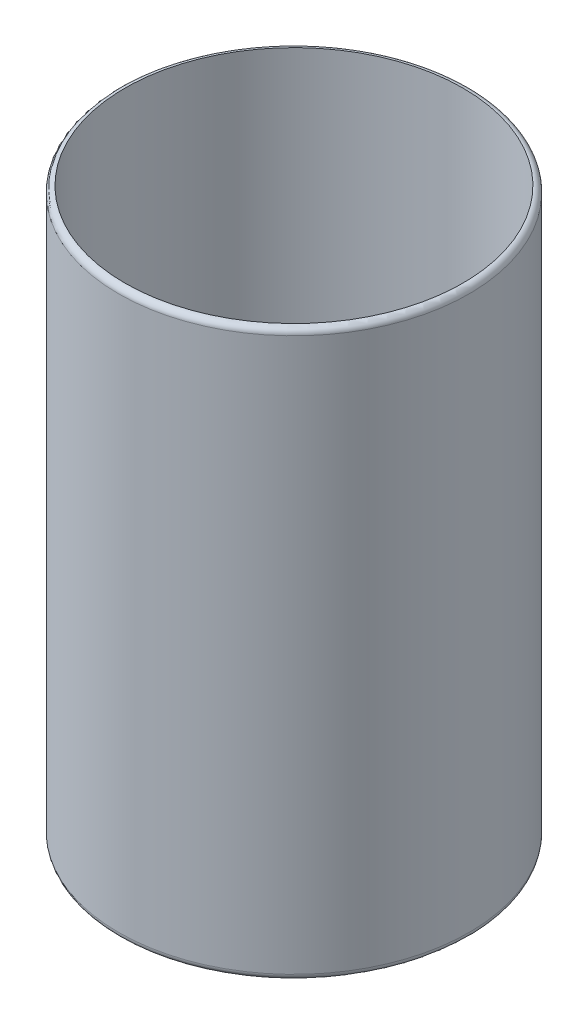
SolidWorks part; units mm, degrees
ref_plane "Front Plane" through (0, 0, 0) normal (0, 0, 1) x (1, 0, 0)
ref_plane "Top Plane" through (0, 0, 0) normal (0, 1, 0) x (1, 0, 0)
ref_plane "Right Plane" through (0, 0, 0) normal (1, 0, 0) x (0, 0, -1)
sketch "Sketch1" plane through (0, 0, 0) normal (0, 1, 0) x (1, 0, 0)
  circle A0 centre (0, 0) radius 14.1
  dimension "D1" = 28.2
extrude "Boss-Extrude1" add sketch "Sketch1" along normal blind 0.5
sketch "Sketch2" plane through (0, 0.5, 0) normal (0, 1, 0) x (1, 0, 0)
  circle A0 centre (0, 0) radius 13.6
  circle A1 centre (0, 0) radius 14.1
  circle A2 centre (0, 0) radius 14.1
  dimension "D1" = 0
  dimension "D2" = 0.5
extrude "Boss-Extrude2" add sketch "Sketch2" along normal blind 45
fillet "Fillet1" radius 0.5 2 edges at (0, 0, 14.1) (0, 0.5, 13.6)
fillet "Fillet2" radius 0.5 1 edges at (0, 45.5, 14.1)
